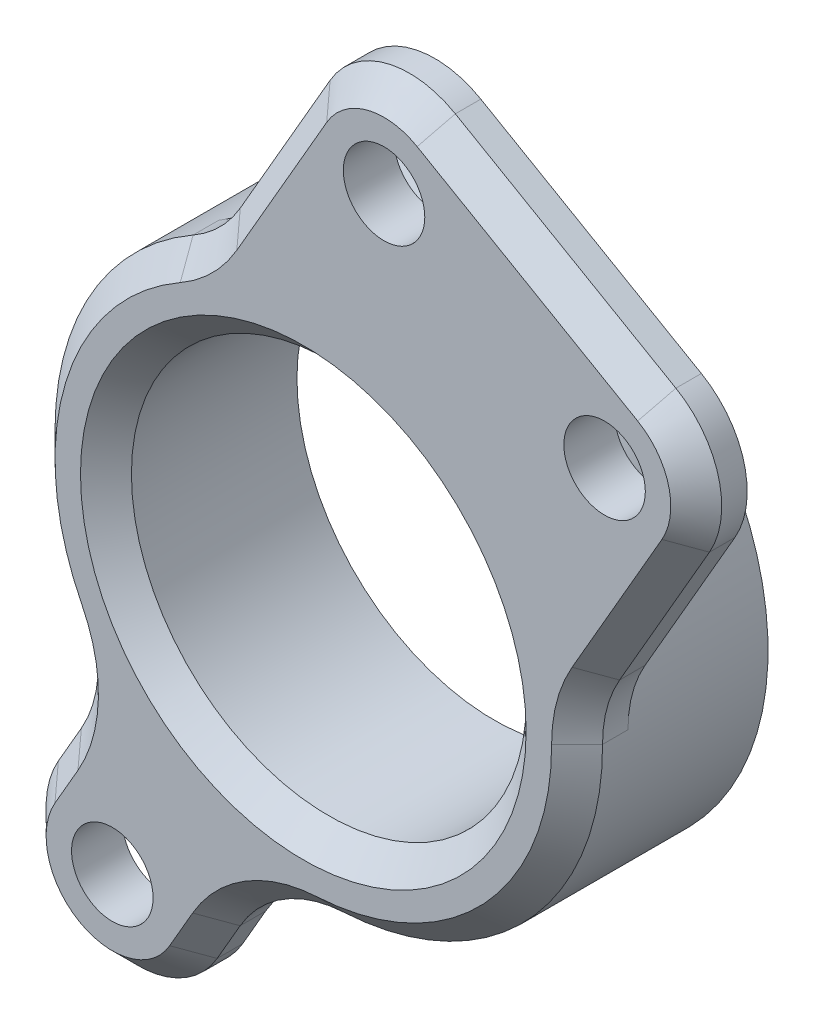
SolidWorks part; units mm, degrees
ref_plane "Front Plane" through (0, 0, 0) normal (0, 0, 1) x (1, 0, 0)
ref_plane "Top Plane" through (0, 0, 0) normal (0, 1, 0) x (1, 0, 0)
ref_plane "Right Plane" through (0, 0, 0) normal (1, 0, 0) x (0, 0, -1)
ref_axis "X" through (-88.99, 0, 0) along (1, 0, 0)
ref_axis "Y" through (0, 55, 0) along (0, -1, 0)
ref_axis "Z" through (0, 0, -88.99) along (0, 0, 1)
sketch "Sketch1" plane through (0, 0, 0) normal (0, 0, 1) x (1, 0, 0)
  line L0 (4.9699, 18.6081) -> (13.6301, 13.6081)
  line L1 (14.9478, 8.6904) -> (10.6728, 1.2859)
  line L2 (0.0522, 17.2904) -> (-4.2228, 9.8859)
  line L3 (-4.3823, -14.7904) -> (-1.947, -10.5722)
  line L4 (-10.6177, -11.1904) -> (-8.1823, -6.9722)
  circle A1 centre (-7.5, -12.9904) radius 1.6 construction
  circle A2 centre (11.8301, 10.4904) radius 1.6 construction
  circle A3 centre (3.1699, 15.4904) radius 1.6 construction
  circle A4 centre (0, 0) radius 11.25 construction
  circle A5 centre (-7.5, -12.9904) radius 1.6
  circle A6 centre (11.8301, 10.4904) radius 1.6
  circle A7 centre (3.1699, 15.4904) radius 1.6
  circle A8 centre (0, 0) radius 11.25 construction
  circle A9 centre (0, 0) radius 10.75
  circle A10 centre (0, 0) radius 7.75
  arc A11 (13.6301, 13.6081) -> (14.9478, 8.6904) centre (11.8301, 10.4904) cw
  arc A12 (4.9699, 18.6081) -> (0.0522, 17.2904) centre (3.1699, 15.4904) ccw
  arc A13 (-10.6177, -11.1904) -> (-4.3823, -14.7904) centre (-7.5, -12.9904) ccw
  dimension "D1" = 0.5
  dimension "D3" = 2
  dimension "D4" = 2
  dimension "D2" = 3
extrude "Boss-Extrude1" add sketch "Sketch1" along normal blind 2 contours L4 A13 L3 A9 A5 | L0 A12 L2 A9 L1 A11 A6 A7 | A9 A10 region at (6.8311, 11.8318, 0) region at (5.223, 9.0465, 0) region at (-5.4414, -9.4248, 0)
extrude "Boss-Extrude2" add sketch "Sketch1<3>" against normal offset from surface (5.5 mm away) 0.5 contours A9 A10 region at (5.223, 9.0465, 0)
sketch "Sketch1<3>" plane through (0, 0, 0) normal (0, 0, 1) x (1, 0, 0) same geometry as "Sketch1"
fillet "Fillet1" radius 5 4 edges at (-4.2228, 9.8859, 1) (-8.1823, -6.9722, 1) (-1.947, -10.5722, 1) (10.6728, 1.2859, 1)
chamfer "Chamfer1" distance 1 angle 45 15 edges at (7.75, 0, 2) (-9.3, -16.1081, 2) (-10.1664, -10.4087, 2) (-3.931, -14.0087, 2) (-9.047, -7.2621, 2) (-1.7656, -11.466, 2) (-10.297, 3.0877, 2) (7.8225, -7.3736, 2) (-4.2795, 10.135, 2) (10.9169, 1.3614, 2) (-1.7119, 14.2349, 2) (13.1837, 5.6349, 2) (2.2381, 18.9677, 2) (15.3075, 11.4221, 2) (9.3, 16.1081, 2)
